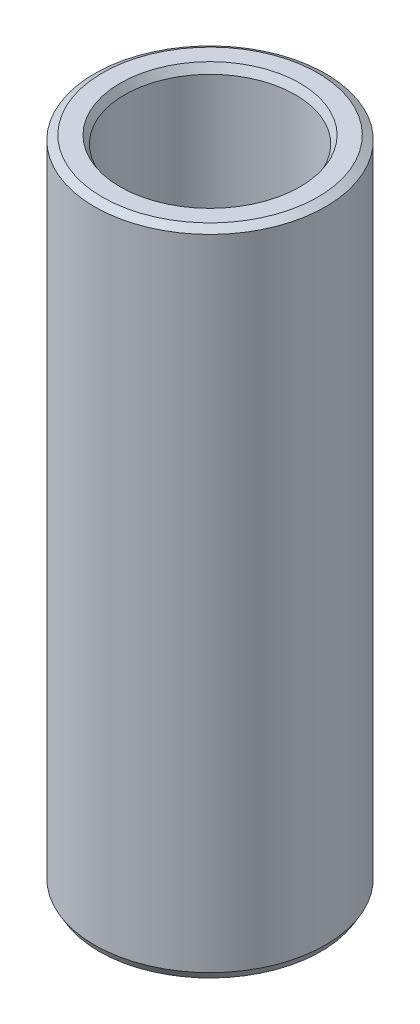
SolidWorks part; units mm, degrees
ref_plane "Front Plane" through (0, 0, 0) normal (0, 0, 1) x (1, 0, 0)
ref_plane "Top Plane" through (0, 0, 0) normal (0, 1, 0) x (1, 0, 0)
ref_plane "Right Plane" through (0, 0, 0) normal (1, 0, 0) x (0, 0, -1)
sketch "Sketch1" plane through (0, 0, 0) normal (0, 1, 0) x (1, 0, 0)
  circle A0 centre (0, 0) radius 55
  dimension "SLEEVE_OD" = 110
extrude "Boss-Extrude1" add sketch "Sketch1" along normal blind 310.4422
sketch "Sketch2" plane through (0, 0, 0) normal (0, 1, 0) x (1, 0, 0)
  circle A0 centre (0, 0) radius 40.6717
  dimension "BORE_D" = 81.3435
extrude "Cut-Extrude1" cut sketch "Sketch2" along normal through all
chamfer "Chamfer1" distance 2.1414 angle 60 4 edges at (0, 310.4422, 40.6717) (0, 0, 40.6717) (0, 0, 55) (0, 310.4422, 55) first distance on face at (0, 310.4422, 40.6717) first distance on face at (0, 0, 40.6717) first distance on face at (0, 310.4422, 55)
